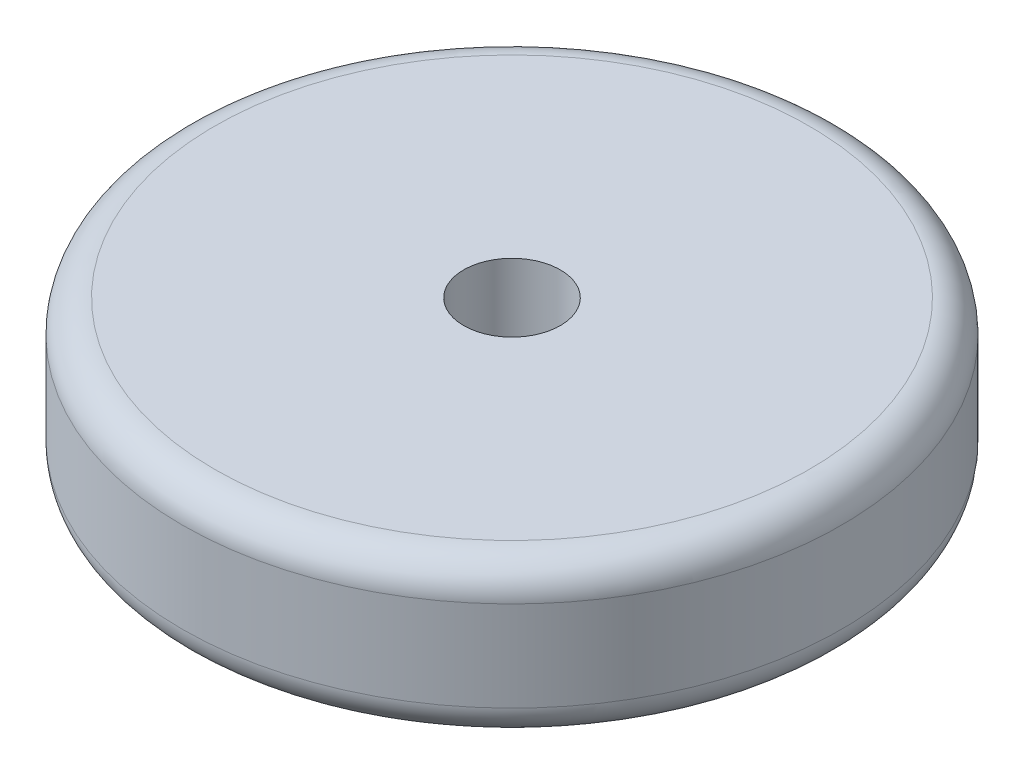
SolidWorks part; units mm, degrees
material "ALUMINUM 6061-T6"
ref_plane "Front Plane" through (0, 0, 0) normal (0, 0, 1) x (1, 0, 0)
ref_plane "Top Plane" through (0, 0, 0) normal (0, 1, 0) x (1, 0, 0)
ref_plane "Right Plane" through (0, 0, 0) normal (1, 0, 0) x (0, 0, -1)
sketch "Sketch1" plane through (0, 0, 0) normal (0, 1, 0) x (1, 0, 0)
  circle A0 centre (0, 0) radius 64.9605
  dimension "D1" = 129.921
extrude "Boss-Extrude1" add sketch "Sketch1" along normal mid plane 30.48
sketch "Sketch2" plane through (0, 15.24, 0) normal (0, 1, 0) x (1, 0, 0)
  circle A0 centre (0, 0) radius 9.525
  dimension "D1" = 19.05
extrude "Cut-Extrude1" cut sketch "Sketch2" against normal blind 30.48
fillet "Fillet1" radius 6.35 2 edges at (0, -15.24, 64.9605) (0, 15.24, 64.9605)
